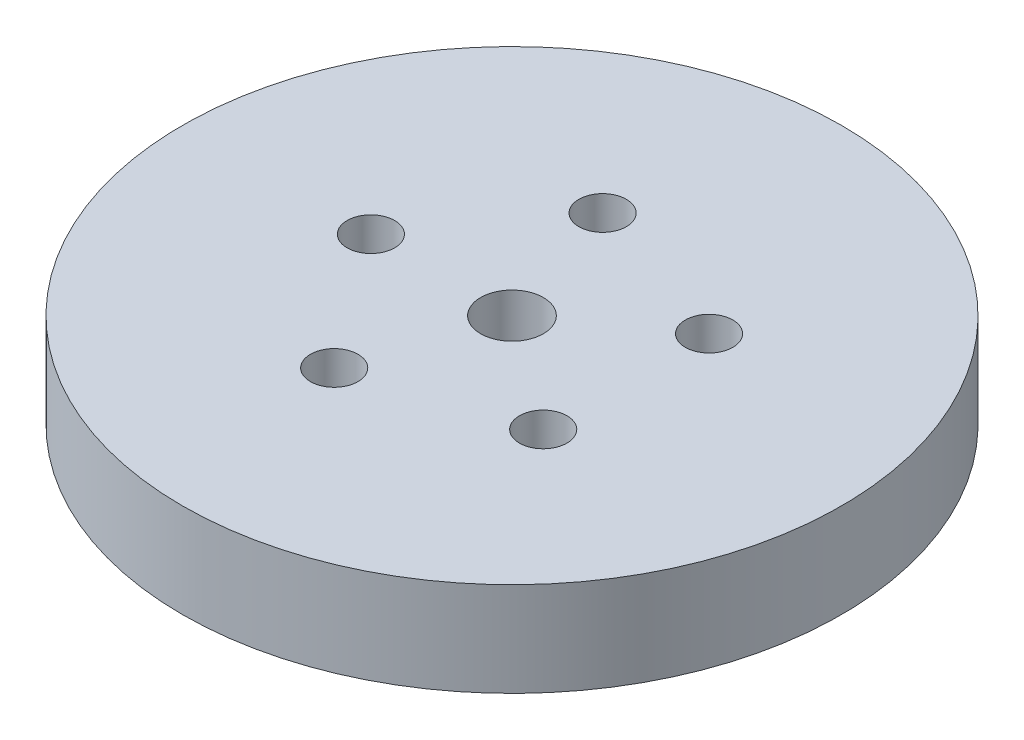
SolidWorks part; units mm, degrees
ref_plane "Front Plane" through (0, 0, 0) normal (0, 0, 1) x (1, 0, 0)
ref_plane "Top Plane" through (0, 0, 0) normal (0, 1, 0) x (1, 0, 0)
ref_plane "Right Plane" through (0, 0, 0) normal (1, 0, 0) x (0, 0, -1)
sketch "Sketch1" plane through (0, 0, 0) normal (0, 1, 0) x (1, 0, 0)
  circle A0 centre (0, 0) radius 52.5
  dimension "FLANGE_OD" = 105
extrude "Boss-Extrude1" add sketch "Sketch1" along normal blind 15
sketch "Sketch2" plane through (0, 0, 0) normal (0, 1, 0) x (1, 0, 0)
  circle A0 centre (0, 0) radius 5
  dimension "BORE_D" = 10
extrude "Cut-Extrude1" cut sketch "Sketch2" along normal through all
sketch "Sketch3" plane through (0, 15, 0) normal (0, 1, 0) x (1, 0, 0)
  circle A0 centre (0, 0) radius 22.4775 construction
  circle A1 centre (-22.4775, 0) radius 3.7831
  dimension "BOLT_D" = 7.5662
  dimension "BOLT_PCD" = 44.9551
extrude "Cut-Extrude2" cut sketch "Sketch3" against normal blind 12.4838
pattern_circular "CirPattern1" count 5 over 360 about axis through (0, 0, 0) along (0, 1, 0) of "Cut-Extrude2"
